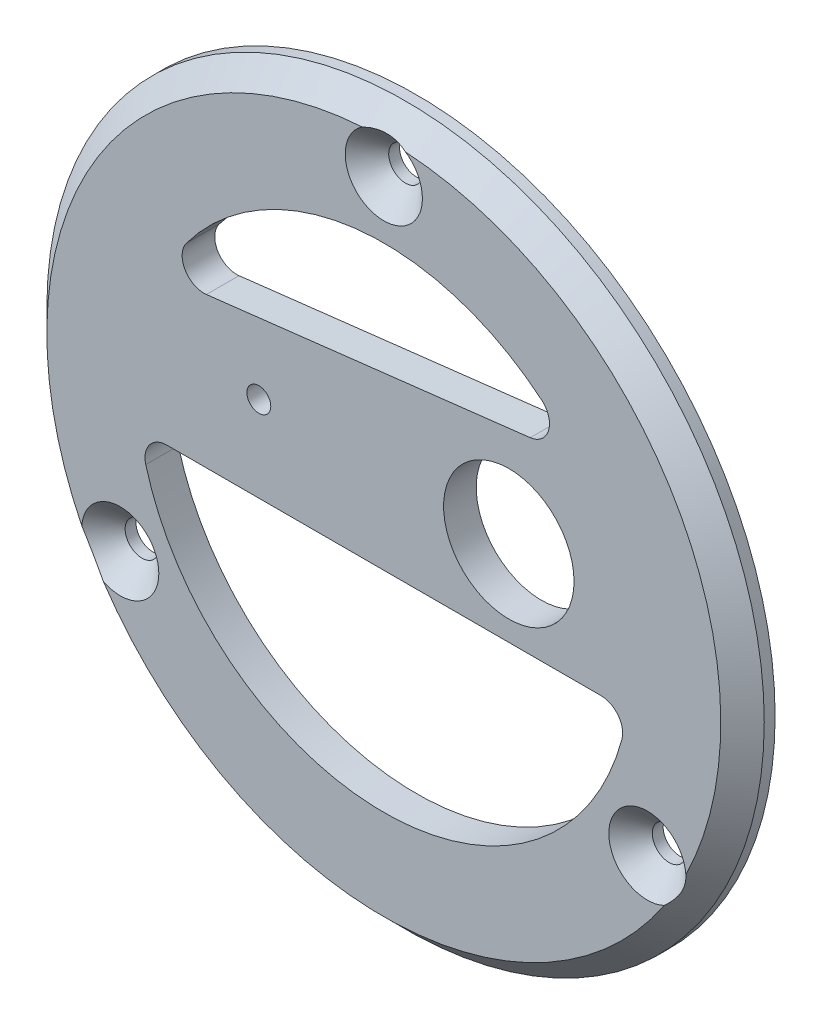
SolidWorks part; units mm, degrees
ref_plane "Front" through (0, 0, 0) normal (0, 0, 1) x (1, 0, 0)
ref_plane "Top" through (0, 0, 0) normal (0, 1, 0) x (1, 0, 0)
ref_plane "Right" through (0, 0, 0) normal (1, 0, 0) x (0, 0, -1)
sketch "Sketch1" plane through (0, 0, 0) normal (0, 0, 1) x (1, 0, 0)
  line L0 (-11.5, 19.9186) -> (0, 0) construction
  line L5 (0, 0) -> (11.5, 19.9186) construction
  line L6 (0, 0) -> (35.9974, 0) construction
  circle A1 centre (0, 0) radius 12.45
  circle A2 centre (0, 0) radius 15.45
  circle A3 centre (11.5, 19.9186) radius 1.05
  circle A4 centre (-11.5, 19.9186) radius 1.05
  circle A5 centre (-11.5, 19.9186) radius 4.05
  circle A6 centre (11.5, 19.9186) radius 4.05
  circle A7 centre (0, 15.45) radius 30
  circle A8 centre (-11.5, 19.9186) radius 12.5 construction
  circle A9 centre (11.5, 19.9186) radius 5 construction
  circle A10 centre (0, 15.45) radius 33
  dimension "D1" = 24.9
  dimension "D2" = 3
  dimension "D7" = 2.1
  dimension "D8" = 2.1
  dimension "D9" = 3
  dimension "D10" = 3
  dimension "D11" = 10
  dimension "D12" = 25
  dimension "D13" = 60
  dimension "D14" = 3
  dimension "D3" = 60
  dimension "D4" = 60
  dimension "D5" = 23
  dimension "D6" = 23
extrude "Boss-Extrude2" add sketch "Sketch1" along normal blind 12.4 contours A10 A7 A2 | A6 A3 | A5 A4 | A7 A2 | A2 A7 A1 region at (12.8555, -7.7664, 0) region at (0, -14.7357, 0) region at (-15.4354, 19.9186, 0) region at (7.5646, 19.9186, 0) region at (-32.0666, 15.45, 0)
sketch "Sketch2" plane through (0, 0, 0) normal (0, 0, -1) x (-1, 0, 0)
  circle A0 centre (0, 15.45) radius 33
  arc A1 (7.1877, -13.6762) -> (-7.1877, -13.6762) centre (0, 0) ccw construction
extrude "Boss-Extrude3" add sketch "Sketch2" along normal blind 3
sketch "Sketch3" plane through (0, 0, 12.4) normal (0, 0, 1) x (1, 0, 0)
  circle A0 centre (0, 15.45) radius 33
  circle A2 centre (0, 15.45) radius 33 construction
  circle A3 centre (0, 15.45) radius 30
extrude "Boss-Extrude4" add sketch "Sketch3" along normal blind 28.6
fillet "Fillet1" radius 10 2 edges at (7.1877, -13.6762, 6.2) (-7.1877, -13.6762, 6.2)
sketch "Sketch4" plane through (0, 0, 0) normal (0, 0, 1) x (1, 0, 0)
  line L0 (-15.356, 18.68) -> (-12.1402, 9.5561)
  line L1 (12.1402, 9.5561) -> (15.356, 18.68)
  line L2 (8.1604, 22.2098) -> (0, 15.45)
  line L3 (-8.1604, 22.2098) -> (0, 15.45)
  line L4 (-8.1604, 22.2098) -> (-10.091, 17.8303)
  line L5 (-10.091, 17.8303) -> (-15.356, 18.68)
  line L6 (8.1604, 22.2098) -> (9.704, 17.8303)
  line L7 (9.704, 17.8303) -> (15.356, 18.68)
  line L8 (-12.1402, 9.5561) -> (-4.4574, 12.839)
  line L9 (-4.4574, 12.839) -> (4.0802, 12.839)
  line L10 (4.0802, 12.839) -> (12.1402, 9.5561)
  arc A0 (12.1402, 9.5561) -> (-12.1402, 9.5561) centre (0, 0) ccw construction
  circle A1 centre (-11.5, 19.9186) radius 4.05 construction
  circle A2 centre (11.5, 19.9186) radius 4.05 construction
extrude "Boss-Extrude5" add sketch "Sketch4" along normal blind 12.4
chamfer "Chamfer1" distance 4 angle 45 3 edges at (23.3394, 6.3161, 0) (-23.3394, 6.3161, 0) (0, 45.45, 0)
fillet "Fillet2" radius 5 2 edges at (-13.385, 23.5032, 0) (13.385, 23.5032, 0)
sketch "Sketch5" plane through (0, 0, 12.4) normal (0, 0, 1) x (1, 0, 0)
  line L0 (0, 15.45) -> (-25.9808, 0.45) construction
  line L1 (0, 15.45) -> (25.9808, 0.45) construction
  line L2 (0, 15.45) -> (0, 45.45) construction
  circle A0 centre (0, 15.45) radius 30 construction
  arc A1 (29.9968, 15.8869) -> (-29.9968, 15.8869) centre (0, 15.45) ccw construction
  circle A2 centre (0, 43.45) radius 4.55
  circle A3 centre (0, 43.45) radius 1.55
  circle A4 centre (24.2487, 1.45) radius 4.55
  circle A5 centre (24.2487, 1.45) radius 1.55
  circle A6 centre (-24.2487, 1.45) radius 4.55
  circle A7 centre (-24.2487, 1.45) radius 1.55
  point P22 (0, 15.45)
  dimension "D3" = 3.1
  dimension "D4" = 3
  dimension "D1" = 120
  dimension "D2" = 120
  dimension "D5" = 28
  dimension "D6" = 3
extrude "Boss-Extrude6" add sketch "Sketch5" along normal up to surface (28.6 mm away) and the other way blind 14.4 up to face at (33, 15.45, 41)
fillet "Fillet3" radius 5 6 edges at (23.6126, -3.0553, 26.7) (27.8324, 4.2536, 26.7) (-23.6126, -3.0553, 26.7) (-27.8324, 4.2536, 26.7) (4.2198, 45.1517, 22.5) (-4.2198, 45.1517, 22.5)
chamfer "Chamfer2" distance 2 angle 45 1 edges at (-33, 15.45, -3)
sketch "Sketch6" plane through (0, 0, 12.4) normal (0, 0, 1) x (1, 0, 0)
  line L1 (-2, -12.0349) -> (2, -12.0349)
  line L2 (-2, -12.0349) -> (-2, -14.0349)
  line L3 (-2, -14.0349) -> (2, -14.0349)
  line L4 (2, -12.0349) -> (2, -14.0349)
  dimension "D1" = 2
extrude "Cut-Extrude1" cut sketch "Sketch6" against normal blind 23.4
sketch "Sketch7" plane through (0, 0, 41) normal (0, 0, 1) x (1, 0, 0)
  circle A0 centre (0, 15.45) radius 33
  circle A2 centre (-24.2487, 1.45) radius 1.55
  circle A3 centre (24.2487, 1.45) radius 1.55
  circle A4 centre (0, 43.45) radius 1.55
  circle A6 centre (11.5, 19.9186) radius 6
  dimension "D1" = 12
extrude "Boss-Extrude7" add sketch "Sketch7" along normal blind 3
sketch "Sketch8" plane through (0, 0, 44) normal (0, 0, 1) x (1, 0, 0)
  circle A0 centre (3.0037, 17.0427) radius 60.265
extrude "Cut-Extrude3" cut sketch "Sketch8" against normal blind 127 from offset 3 offset against normal yes
chamfer "Chamfer3" distance 2 angle 45 1 edges at (33, 15.45, 44)
sketch "Sketch9" plane through (0, 0, 44) normal (0, 0, 1) x (1, 0, 0)
  line L0 (-20.3913, 25.3946) -> (17.5429, 29.8357)
  line L1 (22.4328, 12.0636) -> (-22.4311, 12.052)
  circle A0 centre (0, 15.45) radius 22.687
extrude "Cut-Extrude4" cut sketch "Sketch9" against normal blind 10 contours L0 A0 | L1 A0 region at (-1.9208, 31.8568, 44) region at (0.003, 3.9639, 44)
fillet "Fillet4" radius 2 4 edges at (-22.4311, 12.052, 42.5) (22.4328, 12.0636, 42.5) (17.5429, 29.8357, 42.5) (-20.3913, 25.3946, 42.5)
sketch "Sketch10" plane through (0, 0, 44) normal (0, 0, 1) x (1, 0, 0)
  circle A0 centre (-11.5, 19.9186) radius 1.1
  dimension "D1" = 2.2
extrude "Cut-Extrude5" cut sketch "Sketch10" against normal blind 10
chamfer "Chamfer4" distance 2 angle 45 3 edges at (25.7987, 1.45, 44) (-22.6987, 1.45, 44) (1.55, 43.45, 44)
